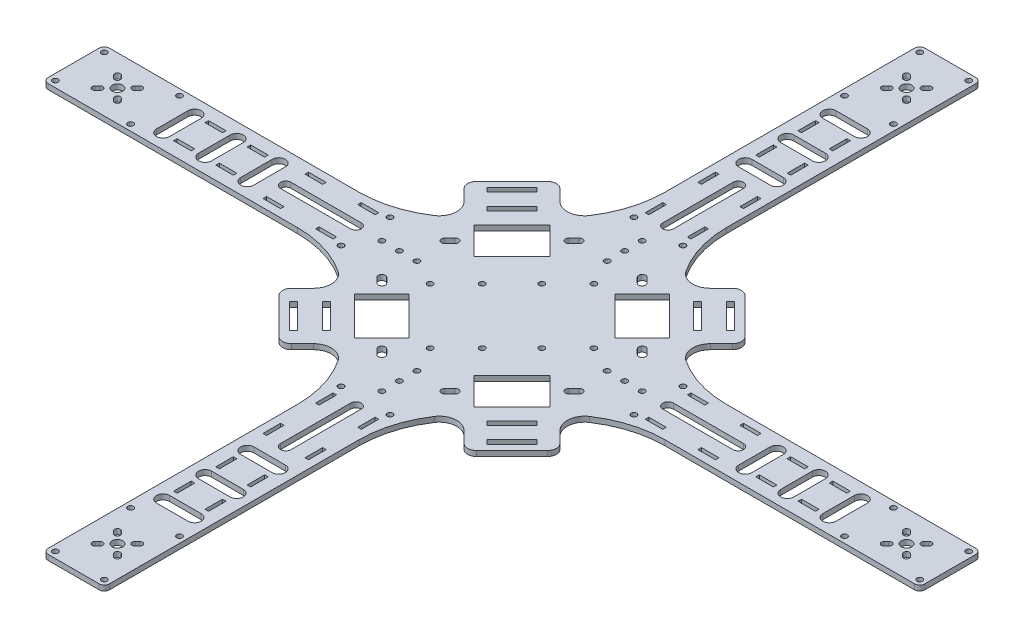
SolidWorks part; units mm, degrees
ref_plane "前视基准面" through (0, 0, 0) normal (0, 0, 1) x (1, 0, 0)
ref_plane "上视基准面" through (0, 0, 0) normal (0, 1, 0) x (1, 0, 0)
ref_plane "右视基准面" through (0, 0, 0) normal (1, 0, 0) x (0, 0, -1)
other "质心 (COM)"
other "Configuration Table"
sketch "基本底盘" plane through (0, 0, 0) normal (0, 1, 0) x (1, 0, 0)
  line L0 (0, 0) -> (0, -450) construction
  line L1 (4.9497, -4.9497) -> (6.364, -6.364) construction
  line L4 (6.0811, -3.8184) -> (7.4953, -5.2326)
  line L5 (3.8184, -6.0811) -> (5.2326, -7.4953)
  line L6 (-17.5, 25) -> (17.5, 25)
  line L9 (-4.9497, -4.9497) -> (-6.364, -6.364) construction
  line L10 (-3.8184, -6.0811) -> (-5.2326, -7.4953)
  line L11 (-6.0811, -3.8184) -> (-7.4953, -5.2326)
  line L12 (-17.5, 25) -> (-17.5, -25)
  line L15 (-4.9497, 4.9497) -> (-6.364, 6.364) construction
  line L16 (-6.0811, 3.8184) -> (-7.4953, 5.2326)
  line L17 (-3.8184, 6.0811) -> (-5.2326, 7.4953)
  line L18 (17.5, 25) -> (17.5, -25)
  line L21 (4.9497, 4.9497) -> (6.364, 6.364) construction
  line L22 (3.8184, 6.0811) -> (5.2326, 7.4953)
  line L23 (6.0811, 3.8184) -> (7.4953, 5.2326)
  line L24 (0, -25) -> (0, -35)
  line L25 (-9, -35) -> (9, -35) construction
  line L26 (-9, -59) -> (9, -59) construction
  line L27 (-17.5, -25) -> (17.5, -25) construction
  line L28 (-17.5, 25) -> (17.5, -25) construction
  line L29 (17.5, 25) -> (-17.5, -25) construction
  line L30 (-17.5, 25) -> (-13.9645, 21.4645)
  line L31 (-17.5, 0) -> (17.5, 0) construction
  line L36 (-225, -225) -> (225, -225) construction
  line L38 (-13.9645, -21.4645) -> (-13.9645, -95) construction
  line L39 (-17.5, -25) -> (-17.5, -120.1472)
  line L40 (17.5, -25) -> (17.5, -120.1472)
  line L42 (-9, -31.25) -> (9, -31.25)
  line L43 (-9, -38.75) -> (9, -38.75)
  line L44 (-9, -55.25) -> (9, -55.25)
  line L45 (-9, -62.75) -> (9, -62.75)
  line L46 (-9, -83) -> (9, -83) construction
  line L47 (-9, -79.25) -> (9, -79.25)
  line L48 (-9, -86.75) -> (9, -86.75)
  line L49 (9, -38.75) -> (9, -55.25)
  line L50 (7.939, -42) -> (9.939, -42)
  line L51 (7.939, -42) -> (7.939, -52)
  line L52 (9.939, -42) -> (9.939, -52)
  line L53 (7.939, -52) -> (9.939, -52)
  line L54 (7.939, -42) -> (9.939, -52) construction
  line L55 (9.939, -42) -> (7.939, -52) construction
  line L56 (7.939, -66.0412) -> (9.939, -76.0412) construction
  line L57 (9.939, -66.0412) -> (7.939, -76.0412) construction
  line L58 (7.939, -66.0412) -> (9.939, -66.0412)
  line L59 (7.939, -66.0412) -> (7.939, -76.0412)
  line L60 (7.939, -76.0412) -> (9.939, -76.0412)
  line L61 (9.939, -66.0412) -> (9.939, -76.0412)
  line L62 (-7.939, -66.0412) -> (-7.939, -76.0412)
  line L63 (-7.939, -76.0412) -> (-9.939, -76.0412)
  line L64 (-9.939, -66.0412) -> (-9.939, -76.0412)
  line L65 (-7.939, -66.0412) -> (-9.939, -66.0412)
  line L66 (-7.939, -52) -> (-9.939, -52)
  line L67 (-7.939, -42) -> (-7.939, -52)
  line L68 (-7.939, -42) -> (-9.939, -42)
  line L69 (-9.939, -42) -> (-9.939, -52)
  line L90 (0, -136) -> (0, -96) construction
  line L92 (-3, -136) -> (-3, -96)
  line L93 (3, -136) -> (3, -96)
  line L94 (11, -96) -> (13, -96)
  line L95 (13, -96) -> (13, -106)
  line L96 (11, -106) -> (13, -106)
  line L97 (11, -96) -> (11, -106)
  line L98 (-11, -96) -> (-11, -106)
  line L99 (-11, -106) -> (-13, -106)
  line L100 (-13, -96) -> (-13, -106)
  line L101 (-11, -96) -> (-13, -96)
  line L102 (-17.5, -116) -> (17.5, -116) construction
  line L103 (-11, -136) -> (-13, -136)
  line L104 (-13, -136) -> (-13, -126)
  line L105 (-11, -126) -> (-13, -126)
  line L106 (-11, -136) -> (-11, -126)
  line L107 (11, -136) -> (11, -126)
  line L108 (11, -126) -> (13, -126)
  line L109 (13, -136) -> (13, -126)
  line L110 (11, -136) -> (13, -136)
  line L111 (250, -207.5) -> (250, -242.5)
  line L112 (250, -207.5) -> (200, -207.5)
  line L113 (250, -242.5) -> (200, -242.5)
  line L114 (200, -225) -> (190, -225)
  line L115 (250, -207.5) -> (246.4645, -211.0355)
  line L116 (200, -207.5) -> (104.8528, -207.5)
  line L117 (200, -242.5) -> (104.8528, -242.5)
  line L118 (186.25, -234) -> (169.75, -234)
  line L119 (183, -232.939) -> (183, -234.939)
  line L120 (183, -232.939) -> (173, -232.939)
  line L121 (183, -234.939) -> (173, -234.939)
  line L122 (173, -232.939) -> (173, -234.939)
  line L123 (158.9588, -232.939) -> (158.9588, -234.939)
  line L124 (158.9588, -232.939) -> (148.9588, -232.939)
  line L125 (148.9588, -232.939) -> (148.9588, -234.939)
  line L126 (158.9588, -234.939) -> (148.9588, -234.939)
  line L127 (158.9588, -217.061) -> (148.9588, -217.061)
  line L128 (148.9588, -217.061) -> (148.9588, -215.061)
  line L129 (158.9588, -215.061) -> (148.9588, -215.061)
  line L130 (158.9588, -217.061) -> (158.9588, -215.061)
  line L131 (173, -217.061) -> (173, -215.061)
  line L132 (183, -217.061) -> (173, -217.061)
  line L133 (183, -217.061) -> (183, -215.061)
  line L134 (183, -215.061) -> (173, -215.061)
  line L135 (129, -236) -> (129, -238)
  line L136 (129, -238) -> (119, -238)
  line L137 (119, -236) -> (119, -238)
  line L138 (129, -236) -> (119, -236)
  line L139 (129, -214) -> (119, -214)
  line L140 (119, -214) -> (119, -212)
  line L141 (129, -212) -> (119, -212)
  line L142 (129, -214) -> (129, -212)
  line L143 (89, -214) -> (89, -212)
  line L144 (89, -212) -> (99, -212)
  line L145 (99, -214) -> (99, -212)
  line L146 (89, -214) -> (99, -214)
  line L147 (89, -236) -> (99, -236)
  line L148 (99, -236) -> (99, -238)
  line L149 (89, -238) -> (99, -238)
  line L150 (89, -236) -> (89, -238)
  line L151 (200, -207.5) -> (200, -242.5) construction
  line L152 (250, -207.5) -> (200, -242.5) construction
  line L153 (250, -242.5) -> (200, -207.5) construction
  line L154 (225, -207.5) -> (225, -242.5) construction
  line L155 (203.5355, -211.0355) -> (130, -211.0355) construction
  line L156 (183, -232.939) -> (173, -234.939) construction
  line L157 (183, -234.939) -> (173, -232.939) construction
  line L158 (158.9588, -232.939) -> (148.9588, -234.939) construction
  line L159 (158.9588, -234.939) -> (148.9588, -232.939) construction
  line L160 (109, -207.5) -> (109, -242.5) construction
  line L161 (220.0503, -229.9497) -> (218.636, -231.364) construction
  line L162 (221.1816, -231.0811) -> (219.7674, -232.4953)
  line L163 (218.9189, -228.8184) -> (217.5047, -230.2326)
  line L164 (220.0503, -220.0503) -> (218.636, -218.636) construction
  line L165 (218.9189, -221.1816) -> (217.5047, -219.7674)
  line L166 (221.1816, -218.9189) -> (219.7674, -217.5047)
  line L167 (229.9497, -220.0503) -> (231.364, -218.636) construction
  line L168 (228.8184, -218.9189) -> (230.2326, -217.5047)
  line L169 (231.0811, -221.1816) -> (232.4953, -219.7674)
  line L170 (229.9497, -229.9497) -> (231.364, -231.364) construction
  line L171 (231.0811, -228.8184) -> (232.4953, -230.2326)
  line L172 (228.8184, -231.0811) -> (230.2326, -232.4953)
  line L173 (190, -216) -> (190, -234) construction
  line L174 (193.75, -216) -> (193.75, -234)
  line L175 (186.25, -216) -> (186.25, -234)
  line L176 (166, -216) -> (166, -234) construction
  line L177 (169.75, -216) -> (169.75, -234)
  line L178 (162.25, -216) -> (162.25, -234)
  line L179 (142, -216) -> (142, -234) construction
  line L180 (145.75, -216) -> (145.75, -234)
  line L181 (138.25, -216) -> (138.25, -234)
  line L182 (89, -225) -> (129, -225) construction
  line L183 (89, -222) -> (129, -222)
  line L184 (89, -228) -> (129, -228)
  line L185 (17.5, -475) -> (-17.5, -475)
  line L186 (17.5, -475) -> (17.5, -425)
  line L187 (-17.5, -475) -> (-17.5, -425)
  line L188 (0, -425) -> (0, -415)
  line L189 (17.5, -475) -> (13.9645, -471.4645)
  line L190 (17.5, -425) -> (17.5, -329.8528)
  line L191 (-17.5, -425) -> (-17.5, -329.8528)
  line L192 (-9, -411.25) -> (-9, -394.75)
  line L193 (-7.939, -408) -> (-9.939, -408)
  line L194 (-7.939, -408) -> (-7.939, -398)
  line L195 (-9.939, -408) -> (-9.939, -398)
  line L196 (-7.939, -398) -> (-9.939, -398)
  line L197 (-7.939, -383.9588) -> (-9.939, -383.9588)
  line L198 (-7.939, -383.9588) -> (-7.939, -373.9588)
  line L199 (-7.939, -373.9588) -> (-9.939, -373.9588)
  line L200 (-9.939, -383.9588) -> (-9.939, -373.9588)
  line L201 (7.939, -383.9588) -> (7.939, -373.9588)
  line L202 (7.939, -373.9588) -> (9.939, -373.9588)
  line L203 (9.939, -383.9588) -> (9.939, -373.9588)
  line L204 (7.939, -383.9588) -> (9.939, -383.9588)
  line L205 (7.939, -398) -> (9.939, -398)
  line L206 (7.939, -408) -> (7.939, -398)
  line L207 (7.939, -408) -> (9.939, -408)
  line L208 (9.939, -408) -> (9.939, -398)
  line L209 (-11, -354) -> (-13, -354)
  line L210 (-13, -354) -> (-13, -344)
  line L211 (-11, -344) -> (-13, -344)
  line L212 (-11, -354) -> (-11, -344)
  line L213 (11, -354) -> (11, -344)
  line L214 (11, -344) -> (13, -344)
  line L215 (13, -354) -> (13, -344)
  line L216 (11, -354) -> (13, -354)
  line L217 (11, -314) -> (13, -314)
  line L218 (13, -314) -> (13, -324)
  line L219 (11, -324) -> (13, -324)
  line L220 (11, -314) -> (11, -324)
  line L221 (-11, -314) -> (-11, -324)
  line L222 (-11, -324) -> (-13, -324)
  line L223 (-13, -314) -> (-13, -324)
  line L224 (-11, -314) -> (-13, -314)
  line L225 (17.5, -425) -> (-17.5, -425) construction
  line L226 (17.5, -475) -> (-17.5, -425) construction
  line L227 (-17.5, -475) -> (17.5, -425) construction
  line L228 (17.5, -450) -> (-17.5, -450) construction
  line L229 (13.9645, -428.5355) -> (13.9645, -355) construction
  line L230 (-7.939, -408) -> (-9.939, -398) construction
  line L231 (-9.939, -408) -> (-7.939, -398) construction
  line L232 (-7.939, -383.9588) -> (-9.939, -373.9588) construction
  line L233 (-9.939, -383.9588) -> (-7.939, -373.9588) construction
  line L234 (17.5, -334) -> (-17.5, -334) construction
  line L235 (-4.9497, -445.0503) -> (-6.364, -443.636) construction
  line L236 (-6.0811, -446.1816) -> (-7.4953, -444.7674)
  line L237 (-3.8184, -443.9189) -> (-5.2326, -442.5047)
  line L238 (4.9497, -445.0503) -> (6.364, -443.636) construction
  line L239 (3.8184, -443.9189) -> (5.2326, -442.5047)
  line L240 (6.0811, -446.1816) -> (7.4953, -444.7674)
  line L241 (4.9497, -454.9497) -> (6.364, -456.364) construction
  line L242 (6.0811, -453.8184) -> (7.4953, -455.2326)
  line L243 (3.8184, -456.0811) -> (5.2326, -457.4953)
  line L244 (-4.9497, -454.9497) -> (-6.364, -456.364) construction
  line L245 (-3.8184, -456.0811) -> (-5.2326, -457.4953)
  line L246 (-6.0811, -453.8184) -> (-7.4953, -455.2326)
  line L247 (9, -415) -> (-9, -415) construction
  line L248 (9, -418.75) -> (-9, -418.75)
  line L249 (9, -411.25) -> (-9, -411.25)
  line L250 (9, -391) -> (-9, -391) construction
  line L251 (9, -394.75) -> (-9, -394.75)
  line L252 (9, -387.25) -> (-9, -387.25)
  line L253 (9, -367) -> (-9, -367) construction
  line L254 (9, -370.75) -> (-9, -370.75)
  line L255 (9, -363.25) -> (-9, -363.25)
  line L256 (0, -314) -> (0, -354) construction
  line L257 (3, -314) -> (3, -354)
  line L258 (-3, -314) -> (-3, -354)
  line L259 (-250, -242.5) -> (-250, -207.5)
  line L260 (-250, -242.5) -> (-200, -242.5)
  line L261 (-250, -207.5) -> (-200, -207.5)
  line L262 (-200, -225) -> (-190, -225)
  line L263 (-250, -242.5) -> (-246.4645, -238.9645)
  line L264 (-200, -242.5) -> (-104.8528, -242.5)
  line L265 (-200, -207.5) -> (-104.8528, -207.5)
  line L266 (-186.25, -216) -> (-169.75, -216)
  line L267 (-183, -217.061) -> (-183, -215.061)
  line L268 (-183, -217.061) -> (-173, -217.061)
  line L269 (-183, -215.061) -> (-173, -215.061)
  line L270 (-173, -217.061) -> (-173, -215.061)
  line L271 (-158.9588, -217.061) -> (-158.9588, -215.061)
  line L272 (-158.9588, -217.061) -> (-148.9588, -217.061)
  line L273 (-148.9588, -217.061) -> (-148.9588, -215.061)
  line L274 (-158.9588, -215.061) -> (-148.9588, -215.061)
  line L275 (-158.9588, -232.939) -> (-148.9588, -232.939)
  line L276 (-148.9588, -232.939) -> (-148.9588, -234.939)
  line L277 (-158.9588, -234.939) -> (-148.9588, -234.939)
  line L278 (-158.9588, -232.939) -> (-158.9588, -234.939)
  line L279 (-173, -232.939) -> (-173, -234.939)
  line L280 (-183, -232.939) -> (-173, -232.939)
  line L281 (-183, -232.939) -> (-183, -234.939)
  line L282 (-183, -234.939) -> (-173, -234.939)
  line L283 (-129, -214) -> (-129, -212)
  line L284 (-129, -212) -> (-119, -212)
  line L285 (-119, -214) -> (-119, -212)
  line L286 (-129, -214) -> (-119, -214)
  line L287 (-129, -236) -> (-119, -236)
  line L288 (-119, -236) -> (-119, -238)
  line L289 (-129, -238) -> (-119, -238)
  line L290 (-129, -236) -> (-129, -238)
  line L291 (-89, -236) -> (-89, -238)
  line L292 (-89, -238) -> (-99, -238)
  line L293 (-99, -236) -> (-99, -238)
  line L294 (-89, -236) -> (-99, -236)
  line L295 (-89, -214) -> (-99, -214)
  line L296 (-99, -214) -> (-99, -212)
  line L297 (-89, -212) -> (-99, -212)
  line L298 (-89, -214) -> (-89, -212)
  line L299 (-200, -242.5) -> (-200, -207.5) construction
  line L300 (-250, -242.5) -> (-200, -207.5) construction
  line L301 (-250, -207.5) -> (-200, -242.5) construction
  line L302 (-225, -242.5) -> (-225, -207.5) construction
  line L303 (-203.5355, -238.9645) -> (-130, -238.9645) construction
  line L304 (-183, -217.061) -> (-173, -215.061) construction
  line L305 (-183, -215.061) -> (-173, -217.061) construction
  line L306 (-158.9588, -217.061) -> (-148.9588, -215.061) construction
  line L307 (-158.9588, -215.061) -> (-148.9588, -217.061) construction
  line L308 (-109, -242.5) -> (-109, -207.5) construction
  line L309 (-220.0503, -220.0503) -> (-218.636, -218.636) construction
  line L310 (-221.1816, -218.9189) -> (-219.7674, -217.5047)
  line L311 (-218.9189, -221.1816) -> (-217.5047, -219.7674)
  line L312 (-220.0503, -229.9497) -> (-218.636, -231.364) construction
  line L313 (-218.9189, -228.8184) -> (-217.5047, -230.2326)
  line L314 (-221.1816, -231.0811) -> (-219.7674, -232.4953)
  line L315 (-229.9497, -229.9497) -> (-231.364, -231.364) construction
  line L316 (-228.8184, -231.0811) -> (-230.2326, -232.4953)
  line L317 (-231.0811, -228.8184) -> (-232.4953, -230.2326)
  line L318 (-229.9497, -220.0503) -> (-231.364, -218.636) construction
  line L319 (-231.0811, -221.1816) -> (-232.4953, -219.7674)
  line L320 (-228.8184, -218.9189) -> (-230.2326, -217.5047)
  line L321 (-190, -234) -> (-190, -216) construction
  line L322 (-193.75, -234) -> (-193.75, -216)
  line L323 (-186.25, -234) -> (-186.25, -216)
  line L324 (-166, -234) -> (-166, -216) construction
  line L325 (-169.75, -234) -> (-169.75, -216)
  line L326 (-162.25, -234) -> (-162.25, -216)
  line L327 (-142, -234) -> (-142, -216) construction
  line L328 (-145.75, -234) -> (-145.75, -216)
  line L329 (-138.25, -234) -> (-138.25, -216)
  line L330 (-89, -225) -> (-129, -225) construction
  line L331 (-89, -228) -> (-129, -228)
  line L332 (-89, -222) -> (-129, -222)
  line L333 (-35.0736, -162.5736) -> (-62.4264, -189.9264) construction
  line L334 (35.0736, -162.5736) -> (62.4264, -189.9264) construction
  line L335 (-62.4264, -260.0736) -> (-35.0736, -287.4264) construction
  line L336 (62.4264, -260.0736) -> (35.0736, -287.4264) construction
  line L337 (-62.4264, -189.9264) -> (-35.0736, -162.5736) construction
  line L338 (-70.2118, -182.141) -> (-80.1041, -172.2487)
  line L339 (-42.859, -154.7882) -> (-52.7513, -144.8959)
  line L340 (-80.1041, -172.2487) -> (-52.7513, -144.8959)
  line L341 (35.0736, -162.5736) -> (62.4264, -189.9264) construction
  line L342 (42.859, -154.7882) -> (52.7513, -144.8959)
  line L343 (52.7513, -144.8959) -> (80.1041, -172.2487)
  line L344 (70.2118, -182.141) -> (80.1041, -172.2487)
  line L345 (62.4264, -260.0736) -> (35.0736, -287.4264) construction
  line L346 (70.2118, -267.859) -> (80.1041, -277.7513)
  line L347 (80.1041, -277.7513) -> (52.7513, -305.1041)
  line L348 (42.859, -295.2118) -> (52.7513, -305.1041)
  line L349 (-35.0736, -287.4264) -> (-62.4264, -260.0736) construction
  line L350 (-42.859, -295.2118) -> (-52.7513, -305.1041)
  line L351 (-52.7513, -305.1041) -> (-80.1041, -277.7513)
  line L352 (-70.2118, -267.859) -> (-80.1041, -277.7513)
  circle A0 centre (0, 0) radius 8 construction
  arc A3 (6.0811, -3.8184) -> (3.8184, -6.0811) centre (4.9497, -4.9497) ccw
  arc A4 (5.2326, -7.4953) -> (7.4953, -5.2326) centre (6.364, -6.364) ccw
  arc A7 (-3.8184, -6.0811) -> (-6.0811, -3.8184) centre (-4.9497, -4.9497) ccw
  arc A8 (-7.4953, -5.2326) -> (-5.2326, -7.4953) centre (-6.364, -6.364) ccw
  arc A11 (-6.0811, 3.8184) -> (-3.8184, 6.0811) centre (-4.9497, 4.9497) ccw
  arc A12 (-5.2326, 7.4953) -> (-7.4953, 5.2326) centre (-6.364, 6.364) ccw
  arc A15 (3.8184, 6.0811) -> (6.0811, 3.8184) centre (4.9497, 4.9497) ccw
  arc A16 (7.4953, 5.2326) -> (5.2326, 7.4953) centre (6.364, 6.364) ccw
  circle A17 centre (0, 0) radius 14 construction
  arc A18 (-9, -31.25) -> (-9, -38.75) centre (-9, -35) ccw
  arc A19 (9, -38.75) -> (9, -31.25) centre (9, -35) ccw
  circle A20 centre (0, 0) radius 3
  circle A21 centre (0, 0) radius 88.9 construction
  circle A22 centre (0, 0) radius 64.77 construction
  circle A23 centre (-13.9645, 21.4645) radius 1.6
  circle A24 centre (13.9645, 21.4645) radius 1.6
  circle A25 centre (13.9645, -21.4645) radius 1.6
  circle A26 centre (-13.9645, -21.4645) radius 1.6
  arc A30 (-9, -55.25) -> (-9, -62.75) centre (-9, -59) ccw
  arc A31 (9, -62.75) -> (9, -55.25) centre (9, -59) ccw
  arc A32 (-9, -79.25) -> (-9, -86.75) centre (-9, -83) ccw
  arc A33 (9, -86.75) -> (9, -79.25) centre (9, -83) ccw
  arc A34 (-3, -136) -> (3, -136) centre (0, -136) ccw
  arc A35 (3, -96) -> (-3, -96) centre (0, -96) ccw
  circle A36 centre (225, -225) radius 3
  circle A37 centre (246.4645, -211.0355) radius 1.6
  circle A38 centre (246.4645, -238.9645) radius 1.6
  circle A39 centre (203.5355, -238.9645) radius 1.6
  circle A40 centre (203.5355, -211.0355) radius 1.6
  circle A41 centre (225, -225) radius 8 construction
  circle A42 centre (225, -225) radius 14 construction
  circle A43 centre (225, -225) radius 88.9 construction
  circle A44 centre (225, -225) radius 64.77 construction
  arc A45 (221.1816, -231.0811) -> (218.9189, -228.8184) centre (220.0503, -229.9497) ccw
  arc A46 (217.5047, -230.2326) -> (219.7674, -232.4953) centre (218.636, -231.364) ccw
  arc A47 (218.9189, -221.1816) -> (221.1816, -218.9189) centre (220.0503, -220.0503) ccw
  arc A48 (219.7674, -217.5047) -> (217.5047, -219.7674) centre (218.636, -218.636) ccw
  arc A49 (228.8184, -218.9189) -> (231.0811, -221.1816) centre (229.9497, -220.0503) ccw
  arc A50 (232.4953, -219.7674) -> (230.2326, -217.5047) centre (231.364, -218.636) ccw
  arc A51 (231.0811, -228.8184) -> (228.8184, -231.0811) centre (229.9497, -229.9497) ccw
  arc A52 (230.2326, -232.4953) -> (232.4953, -230.2326) centre (231.364, -231.364) ccw
  arc A53 (193.75, -216) -> (186.25, -216) centre (190, -216) ccw
  arc A54 (186.25, -234) -> (193.75, -234) centre (190, -234) ccw
  arc A55 (169.75, -216) -> (162.25, -216) centre (166, -216) ccw
  arc A56 (162.25, -234) -> (169.75, -234) centre (166, -234) ccw
  arc A57 (145.75, -216) -> (138.25, -216) centre (142, -216) ccw
  arc A58 (138.25, -234) -> (145.75, -234) centre (142, -234) ccw
  arc A59 (89, -222) -> (89, -228) centre (89, -225) ccw
  arc A60 (129, -228) -> (129, -222) centre (129, -225) ccw
  circle A61 centre (0, -450) radius 3
  circle A62 centre (13.9645, -471.4645) radius 1.6
  circle A63 centre (-13.9645, -471.4645) radius 1.6
  circle A64 centre (-13.9645, -428.5355) radius 1.6
  circle A65 centre (13.9645, -428.5355) radius 1.6
  circle A66 centre (0, -450) radius 8 construction
  circle A67 centre (0, -450) radius 14 construction
  circle A68 centre (0, -450) radius 88.9 construction
  circle A69 centre (0, -450) radius 64.77 construction
  arc A70 (-6.0811, -446.1816) -> (-3.8184, -443.9189) centre (-4.9497, -445.0503) ccw
  arc A71 (-5.2326, -442.5047) -> (-7.4953, -444.7674) centre (-6.364, -443.636) ccw
  arc A72 (3.8184, -443.9189) -> (6.0811, -446.1816) centre (4.9497, -445.0503) ccw
  arc A73 (7.4953, -444.7674) -> (5.2326, -442.5047) centre (6.364, -443.636) ccw
  arc A74 (6.0811, -453.8184) -> (3.8184, -456.0811) centre (4.9497, -454.9497) ccw
  arc A75 (5.2326, -457.4953) -> (7.4953, -455.2326) centre (6.364, -456.364) ccw
  arc A76 (-3.8184, -456.0811) -> (-6.0811, -453.8184) centre (-4.9497, -454.9497) ccw
  arc A77 (-7.4953, -455.2326) -> (-5.2326, -457.4953) centre (-6.364, -456.364) ccw
  arc A78 (9, -418.75) -> (9, -411.25) centre (9, -415) ccw
  arc A79 (-9, -411.25) -> (-9, -418.75) centre (-9, -415) ccw
  arc A80 (9, -394.75) -> (9, -387.25) centre (9, -391) ccw
  arc A81 (-9, -387.25) -> (-9, -394.75) centre (-9, -391) ccw
  arc A82 (9, -370.75) -> (9, -363.25) centre (9, -367) ccw
  arc A83 (-9, -363.25) -> (-9, -370.75) centre (-9, -367) ccw
  arc A84 (3, -314) -> (-3, -314) centre (0, -314) ccw
  arc A85 (-3, -354) -> (3, -354) centre (0, -354) ccw
  circle A86 centre (-225, -225) radius 3
  circle A87 centre (-246.4645, -238.9645) radius 1.6
  circle A88 centre (-246.4645, -211.0355) radius 1.6
  circle A89 centre (-203.5355, -211.0355) radius 1.6
  circle A90 centre (-203.5355, -238.9645) radius 1.6
  circle A91 centre (-225, -225) radius 8 construction
  circle A92 centre (-225, -225) radius 14 construction
  circle A93 centre (-225, -225) radius 88.9 construction
  circle A94 centre (-225, -225) radius 64.77 construction
  arc A95 (-221.1816, -218.9189) -> (-218.9189, -221.1816) centre (-220.0503, -220.0503) ccw
  arc A96 (-217.5047, -219.7674) -> (-219.7674, -217.5047) centre (-218.636, -218.636) ccw
  arc A97 (-218.9189, -228.8184) -> (-221.1816, -231.0811) centre (-220.0503, -229.9497) ccw
  arc A98 (-219.7674, -232.4953) -> (-217.5047, -230.2326) centre (-218.636, -231.364) ccw
  arc A99 (-228.8184, -231.0811) -> (-231.0811, -228.8184) centre (-229.9497, -229.9497) ccw
  arc A100 (-232.4953, -230.2326) -> (-230.2326, -232.4953) centre (-231.364, -231.364) ccw
  arc A101 (-231.0811, -221.1816) -> (-228.8184, -218.9189) centre (-229.9497, -220.0503) ccw
  arc A102 (-230.2326, -217.5047) -> (-232.4953, -219.7674) centre (-231.364, -218.636) ccw
  arc A103 (-193.75, -234) -> (-186.25, -234) centre (-190, -234) ccw
  arc A104 (-186.25, -216) -> (-193.75, -216) centre (-190, -216) ccw
  arc A105 (-169.75, -234) -> (-162.25, -234) centre (-166, -234) ccw
  arc A106 (-162.25, -216) -> (-169.75, -216) centre (-166, -216) ccw
  arc A107 (-145.75, -234) -> (-138.25, -234) centre (-142, -234) ccw
  arc A108 (-138.25, -216) -> (-145.75, -216) centre (-142, -216) ccw
  arc A109 (-89, -228) -> (-89, -222) centre (-89, -225) ccw
  arc A110 (-129, -222) -> (-129, -228) centre (-129, -225) ccw
  circle A111 centre (-13.9645, -141.4645) radius 1.6
  circle A112 centre (13.9645, -141.4645) radius 1.6
  circle A113 centre (83.5355, -211.0355) radius 1.6
  circle A114 centre (83.5355, -238.9645) radius 1.6
  circle A115 centre (13.9645, -308.5355) radius 1.6
  circle A116 centre (-13.9645, -308.5355) radius 1.6
  circle A117 centre (-83.5355, -238.9645) radius 1.6
  circle A118 centre (-83.5355, -211.0355) radius 1.6
  arc A119 (104.8528, -242.5) -> (71.7689, -252.4455) centre (104.8528, -302.5) ccw
  arc A120 (104.8528, -207.5) -> (71.7689, -197.5545) centre (104.8528, -147.5) cw
  arc A121 (17.5, -329.8528) -> (27.4455, -296.7689) centre (77.5, -329.8528) cw
  arc A122 (-17.5, -329.8528) -> (-27.4455, -296.7689) centre (-77.5, -329.8528) ccw
  arc A123 (-71.7689, -252.4455) -> (-104.8528, -242.5) centre (-104.8528, -302.5) ccw
  arc A124 (-104.8528, -207.5) -> (-71.7689, -197.5545) centre (-104.8528, -147.5) ccw
  arc A125 (27.4455, -153.2311) -> (17.5, -120.1472) centre (77.5, -120.1472) cw
  arc A126 (-27.4455, -153.2311) -> (-17.5, -120.1472) centre (-77.5, -120.1472) ccw
  arc A127 (-27.4455, -296.7689) -> (-42.859, -295.2118) centre (-35.7879, -302.2829) ccw
  arc A128 (-70.2118, -267.859) -> (-71.7689, -252.4455) centre (-77.2829, -260.7879) ccw
  arc A129 (70.2118, -267.859) -> (71.7689, -252.4455) centre (77.2829, -260.7879) cw
  arc A130 (27.4455, -296.7689) -> (42.859, -295.2118) centre (35.7879, -302.2829) cw
  arc A131 (71.7689, -197.5545) -> (70.2118, -182.141) centre (77.2829, -189.2121) cw
  arc A132 (42.859, -154.7882) -> (27.4455, -153.2311) centre (35.7879, -147.7171) cw
  arc A133 (-27.4455, -153.2311) -> (-42.859, -154.7882) centre (-35.7879, -147.7171) cw
  arc A134 (-71.7689, -197.5545) -> (-70.2118, -182.141) centre (-77.2829, -189.2121) ccw
  point P14 (5.6569, -5.6569)
  point P28 (-5.6569, -5.6569)
  point P34 (0, 0)
  point P42 (-5.6569, 5.6569)
  point P51 (0, -225)
  point P56 (5.6569, 5.6569)
  point P61 (0, 0)
  point P63 (0, 8)
  point P71 (0, -116)
  point P73 (0, -35)
  point P80 (0, -59)
  point P87 (0, -83)
  point P93 (8.939, -47)
  point P95 (8.939, -71.0412)
  point P124 (0, -116)
  point P143 (219.3431, -230.6569)
  point P157 (219.3431, -219.3431)
  point P163 (225, -225)
  point P171 (230.6569, -219.3431)
  point P181 (230.6569, -230.6569)
  point P186 (225, -225)
  point P195 (109, -225)
  point P196 (190, -225)
  point P203 (166, -225)
  point P210 (142, -225)
  point P216 (178, -233.939)
  point P218 (153.9588, -233.939)
  point P242 (109, -225)
  point P265 (-5.6569, -444.3431)
  point P279 (5.6569, -444.3431)
  point P285 (0, -450)
  point P293 (5.6569, -455.6569)
  point P303 (-5.6569, -455.6569)
  point P308 (0, -450)
  point P317 (0, -334)
  point P318 (0, -415)
  point P325 (0, -391)
  point P332 (0, -367)
  point P338 (-8.939, -403)
  point P340 (-8.939, -378.9588)
  point P364 (0, -334)
  point P387 (-219.3431, -219.3431)
  point P401 (-219.3431, -230.6569)
  point P407 (-225, -225)
  point P415 (-230.6569, -230.6569)
  point P425 (-230.6569, -219.3431)
  point P432 (-225, -225)
  point P441 (-109, -225)
  point P442 (-190, -225)
  point P449 (-166, -225)
  point P456 (-142, -225)
  point P462 (-178, -216.061)
  point P464 (-153.9588, -216.061)
  point P488 (-109, -225)
  point P499 (0, -225)
  point P516 (0, -225)
  point P547 (0, -225)
  dimension "D1" = 16
  dimension "D3" = 28
  dimension "D2" = 6
  dimension "D4" = 4
  dimension "D5" = 129.54
  dimension "D9" = 3.2
  dimension "D11" = 4
  dimension "D12" = 60
  dimension "D13" = 25
  dimension "D14" = 10
  dimension "D15" = 3
  dimension "D20" = 10
  dimension "D10" = 2
  dimension "D6" = 35
  dimension "D7" = 50
  dimension "D8" = 5
  dimension "D16" = 2
  dimension "D17" = 10
  dimension "D19" = 4
  dimension "D18" = 2
extrude "凸台-拉伸1" add sketch "基本底盘" along normal blind 3 contours A126 L333 A124 L265 L261 L259 A87 L260 L264 A123 L335 A122 L191 L187 L185 A62 L186 L190 A121 L336 A119 L117 L113 L111 A37 L112 L116 A120 L334 A125 L40 L18 L6 A23 L12 L39 A118 A115 A114 region at (0, 0, 225)
sketch "草图2" plane through (0, 3, 0) normal (0, 1, 0) x (1, 0, 0)
  line L0 (-17.6777, -207.3223) -> (17.6777, -242.6777)
  line L1 (24.7487, -200.2513) -> (23.3345, -201.6655)
  line L2 (-24.7487, -249.7487) -> (24.7487, -200.2513)
  line L3 (7.0711, -182.5736) -> (42.4264, -217.9289) construction
  line L4 (7.0711, -182.5736) -> (-42.4264, -232.0711) construction
  line L5 (42.4264, -217.9289) -> (-7.0711, -267.4264) construction
  line L6 (-42.4264, -232.0711) -> (-7.0711, -267.4264) construction
  line L7 (7.0711, -182.5736) -> (-7.0711, -267.4264) construction
  line L8 (42.4264, -217.9289) -> (-42.4264, -232.0711) construction
  line L9 (7.4246, -185.7556) -> (39.2444, -217.5754)
  line L10 (17.6777, -242.6777) -> (37.1231, -262.1231)
  line L11 (19.4454, -279.8008) -> (54.8008, -244.4454) construction
  line L12 (56.215, -243.0312) -> (53.3866, -245.8597) construction
  line L13 (18.0312, -281.215) -> (20.8597, -278.3866) construction
  line L14 (57.6292, -244.4454) -> (54.8008, -247.2739)
  line L15 (54.8008, -241.617) -> (51.9723, -244.4454)
  line L16 (19.4454, -282.6292) -> (22.2739, -279.8008)
  line L17 (16.617, -279.8008) -> (19.4454, -276.9723)
  line L18 (-18.0312, -281.215) -> (-20.8597, -278.3866) construction
  line L19 (-19.4454, -282.6292) -> (-22.2739, -279.8008)
  line L20 (-16.617, -279.8008) -> (-19.4454, -276.9723)
  line L21 (-56.215, -243.0312) -> (-53.3866, -245.8597) construction
  line L22 (-57.6292, -244.4454) -> (-54.8008, -247.2739)
  line L23 (-54.8008, -241.617) -> (-51.9723, -244.4454)
  line L24 (-56.215, -206.9688) -> (-53.3866, -204.1403) construction
  line L25 (-57.6292, -205.5546) -> (-54.8008, -202.7261)
  line L26 (-54.8008, -208.383) -> (-51.9723, -205.5546)
  line L27 (-18.0312, -168.785) -> (-20.8597, -171.6134) construction
  line L28 (-19.4454, -167.3708) -> (-22.2739, -170.1992)
  line L29 (-16.617, -170.1992) -> (-19.4454, -173.0277)
  line L30 (18.0312, -168.785) -> (20.8597, -171.6134) construction
  line L31 (19.4454, -167.3708) -> (22.2739, -170.1992)
  line L32 (16.617, -170.1992) -> (19.4454, -173.0277)
  line L33 (56.215, -206.9688) -> (53.3866, -204.1403) construction
  line L34 (57.6292, -205.5546) -> (54.8008, -202.7261)
  line L35 (54.8008, -208.383) -> (51.9723, -205.5546)
  line L36 (18.5616, -265.1283) -> (40.1283, -243.5616)
  line L37 (18.5616, -265.1283) -> (34.1179, -280.6847)
  line L38 (40.1283, -243.5616) -> (55.6847, -259.1179)
  line L39 (34.1179, -280.6847) -> (55.6847, -259.1179)
  line L40 (18.5616, -265.1283) -> (55.6847, -259.1179) construction
  line L41 (40.1283, -243.5616) -> (34.1179, -280.6847) construction
  line L42 (-40.1283, -243.5616) -> (-18.5616, -265.1283)
  line L43 (-40.1283, -243.5616) -> (-55.6847, -259.1179)
  line L44 (-55.6847, -259.1179) -> (-34.1179, -280.6847)
  line L45 (-18.5616, -265.1283) -> (-34.1179, -280.6847)
  line L46 (-18.5616, -184.8717) -> (-40.1283, -206.4384)
  line L47 (-18.5616, -184.8717) -> (-34.1179, -169.3153)
  line L48 (-34.1179, -169.3153) -> (-55.6847, -190.8821)
  line L49 (-40.1283, -206.4384) -> (-55.6847, -190.8821)
  line L50 (40.1283, -206.4384) -> (18.5616, -184.8717)
  line L51 (40.1283, -206.4384) -> (55.6847, -190.8821)
  line L52 (55.6847, -190.8821) -> (34.1179, -169.3153)
  line L53 (18.5616, -184.8717) -> (34.1179, -169.3153)
  line L54 (0, -150.7538) -> (18.0312, -168.785) construction
  line L55 (-19.4454, -170.1992) -> (0, -150.7538) construction
  line L56 (0, 0) -> (0, -450) construction
  line L57 (-66.4277, -158.5723) -> (-57.5888, -167.4112) construction
  line L58 (-80.1041, -172.2487) -> (-52.7513, -144.8959) construction
  line L59 (-64.6599, -174.4822) -> (-50.5178, -160.3401)
  line L60 (-57.5888, -167.4112) -> (-54.0533, -170.9467)
  line L61 (-61.1244, -178.0178) -> (-46.9822, -163.8756)
  line L62 (-46.9822, -163.8756) -> (-44.7195, -166.1384)
  line L63 (-44.7195, -166.1384) -> (-58.8616, -180.2805)
  line L64 (-58.8616, -180.2805) -> (-61.1244, -178.0178)
  line L65 (-56.316, -154.5418) -> (-70.4582, -168.684)
  line L66 (-54.0533, -156.8046) -> (-56.316, -154.5418)
  line L67 (-68.1954, -170.9467) -> (-54.0533, -156.8046)
  line L68 (-70.4582, -168.684) -> (-68.1954, -170.9467)
  line L69 (70.4582, -168.684) -> (56.316, -154.5418)
  line L70 (56.316, -154.5418) -> (54.0533, -156.8046)
  line L71 (54.0533, -156.8046) -> (68.1954, -170.9467)
  line L72 (68.1954, -170.9467) -> (70.4582, -168.684)
  line L73 (44.7195, -166.1384) -> (46.9822, -163.8756)
  line L74 (46.9822, -163.8756) -> (61.1244, -178.0178)
  line L75 (61.1244, -178.0178) -> (58.8616, -180.2805)
  line L76 (58.8616, -180.2805) -> (44.7195, -166.1384)
  line L77 (56.316, -295.4582) -> (70.4582, -281.316)
  line L78 (70.4582, -281.316) -> (68.1954, -279.0533)
  line L79 (68.1954, -279.0533) -> (54.0533, -293.1954)
  line L80 (54.0533, -293.1954) -> (56.316, -295.4582)
  line L81 (58.8616, -269.7195) -> (61.1244, -271.9822)
  line L82 (61.1244, -271.9822) -> (46.9822, -286.1244)
  line L83 (46.9822, -286.1244) -> (44.7195, -283.8616)
  line L84 (44.7195, -283.8616) -> (58.8616, -269.7195)
  line L85 (-70.4582, -281.316) -> (-56.316, -295.4582)
  line L86 (-56.316, -295.4582) -> (-54.0533, -293.1954)
  line L87 (-54.0533, -293.1954) -> (-68.1954, -279.0533)
  line L88 (-68.1954, -279.0533) -> (-70.4582, -281.316)
  line L89 (-44.7195, -283.8616) -> (-46.9822, -286.1244)
  line L90 (-46.9822, -286.1244) -> (-61.1244, -271.9822)
  line L91 (-61.1244, -271.9822) -> (-58.8616, -269.7195)
  line L92 (-58.8616, -269.7195) -> (-44.7195, -283.8616)
  circle A0 centre (39.2444, -217.5754) radius 1.6
  circle A1 centre (7.4246, -185.7556) radius 1.6
  circle A2 centre (7.4246, -249.3952) radius 1.6
  circle A3 centre (-24.3952, -217.5754) radius 1.6
  circle A4 centre (24.3952, -232.4246) radius 1.6
  circle A5 centre (-7.4246, -264.2444) radius 1.6
  circle A6 centre (-39.2444, -232.4246) radius 1.6
  circle A7 centre (-7.4246, -200.6048) radius 1.6
  arc A8 (57.6292, -244.4454) -> (54.8008, -241.617) centre (56.215, -243.0312) ccw
  arc A9 (51.9723, -244.4454) -> (54.8008, -247.2739) centre (53.3866, -245.8597) ccw
  arc A10 (19.4454, -282.6292) -> (16.617, -279.8008) centre (18.0312, -281.215) cw
  arc A11 (19.4454, -276.9723) -> (22.2739, -279.8008) centre (20.8597, -278.3866) cw
  arc A12 (-19.4454, -282.6292) -> (-16.617, -279.8008) centre (-18.0312, -281.215) ccw
  arc A13 (-19.4454, -276.9723) -> (-22.2739, -279.8008) centre (-20.8597, -278.3866) ccw
  arc A14 (-57.6292, -244.4454) -> (-54.8008, -241.617) centre (-56.215, -243.0312) cw
  arc A15 (-51.9723, -244.4454) -> (-54.8008, -247.2739) centre (-53.3866, -245.8597) cw
  arc A16 (-57.6292, -205.5546) -> (-54.8008, -208.383) centre (-56.215, -206.9688) ccw
  arc A17 (-51.9723, -205.5546) -> (-54.8008, -202.7261) centre (-53.3866, -204.1403) ccw
  arc A18 (-19.4454, -167.3708) -> (-16.617, -170.1992) centre (-18.0312, -168.785) cw
  arc A19 (-19.4454, -173.0277) -> (-22.2739, -170.1992) centre (-20.8597, -171.6134) cw
  arc A20 (19.4454, -167.3708) -> (16.617, -170.1992) centre (18.0312, -168.785) ccw
  arc A21 (19.4454, -173.0277) -> (22.2739, -170.1992) centre (20.8597, -171.6134) ccw
  arc A22 (57.6292, -205.5546) -> (54.8008, -208.383) centre (56.215, -206.9688) cw
  arc A23 (51.9723, -205.5546) -> (54.8008, -202.7261) centre (53.3866, -204.1403) cw
  circle A24 centre (0, -150.7538) radius 1.6
  circle A25 centre (0, -160.7538) radius 1.6
  circle A26 centre (0, -170.7538) radius 1.6
  circle A27 centre (74.2462, -225) radius 1.6
  circle A28 centre (64.2462, -225) radius 1.6
  circle A29 centre (54.2462, -225) radius 1.6
  circle A30 centre (0, -299.2462) radius 1.6
  circle A31 centre (0, -289.2462) radius 1.6
  circle A32 centre (0, -279.2462) radius 1.6
  circle A33 centre (-74.2462, -225) radius 1.6
  circle A34 centre (-64.2462, -225) radius 1.6
  circle A35 centre (-54.2462, -225) radius 1.6
  point P3 (0, -225)
  point P7 (0, -225)
  point P8 (0, -225)
  point P12 (23.3345, -201.6655)
  point P34 (37.1231, -262.1231)
  point P38 (54.8008, -244.4454)
  point P43 (19.4454, -279.8008)
  point P55 (-19.4454, -279.8008)
  point P60 (-54.8008, -244.4454)
  point P69 (-54.8008, -205.5546)
  point P74 (-19.4454, -170.1992)
  point P83 (19.4454, -170.1992)
  point P88 (54.8008, -205.5546)
  point P93 (0, -225)
  point P110 (0, -225)
  point P139 (0, -225)
  point P144 (-57.5888, -167.4112)
  point P148 (-54.0533, -170.9467)
  point P181 (0, -225)
  dimension "D4" = 3.2
  dimension "D5" = 3.2
  dimension "D13" = 3.2
  dimension "D1" = 70
  dimension "D2" = 2
  dimension "D3" = 22.5
  dimension "D7" = 27.5
  dimension "D8" = 25
  dimension "D9" = 4
  dimension "D10" = 30.5
  dimension "D11" = 22
  dimension "D16" = 12.5
  dimension "D17" = 10
  dimension "D18" = 5
  dimension "D19" = 10
  dimension "D20" = 3.2
  dimension "D21" = 20
  dimension "D22" = 4
  dimension "D6" = 2
  dimension "D14" = 3
  dimension "D12" = 4
  dimension "D15" = 4
extrude "切除-拉伸1" cut sketch "草图2" against normal blind 10 and the other way through all contours L49 L46 L47 L48 | L53 L50 L51 L52 | A24 | A25 | A26 | L32 A21 L31 A20 | A19 L29 A18 L28 | L26 A17 L25 A16 | A23 L35 A22 L34 | L15 A9 L14 A8 | L37 L39 L38 L36 | A7 | A1 | A3 | A6 | A34 | A33 | A35 | A15 L23 A14 L22 | L45 L42 L43 L44 | A11 L17 A10 L16 | A32 | A31 | L20 A13 L19 A12 | A30 | A5 | A2 | A4 | A0 | A29 | A28 | A27 | A7 region at (35.1079, 3, 249.3245) region at (5.9882, 3, 185.1606) region at (39.8394, 3, 216.139) region at (54.8008, 3, 244.4454) region at (19.4454, 3, 279.8008) region at (-19.4454, 3, 279.8008) region at (-54.8008, 3, 244.4454) region at (-54.8008, 3, 205.5546) region at (-19.4454, 3, 170.1992) region at (19.4454, 3, 170.1992) region at (54.8008, 3, 205.5546) region at (-37.1231, 3, 262.1231) region at (-37.1231, 3, 187.8769) region at (37.1231, 3, 187.8769) region at (7.4246, 3, 249.3952) region at (-24.3952, 3, 217.5754) region at (24.3952, 3, 232.4246) region at (-7.4246, 3, 264.2444) region at (-39.2444, 3, 232.4246) region at (-7.4246, 3, 200.6048) region at (0, 3, 150.7538) region at (0, 3, 160.7538) region at (0, 3, 170.7538) region at (74.2462, 3, 225) region at (64.2462, 3, 225) region at (54.2462, 3, 225) region at (0, 3, 299.2462) region at (0, 3, 289.2462) region at (0, 3, 279.2462) region at (-74.2462, 3, 225) region at (-64.2462, 3, 225) region at (-54.2462, 3, 225)
fillet "圆角1" radius 3 8 edges at (-250, 1.5, 242.5) (-250, 1.5, 207.5) (250, 1.5, 242.5) (250, 1.5, 207.5) (-17.5, 1.5, -25) (17.5, 1.5, -25) (17.5, 1.5, 475) (-17.5, 1.5, 475)
fillet "圆角2" radius 5 8 edges at (-80.1041, 1.5, 172.2487) (-52.7513, 1.5, 144.8959) (52.7513, 1.5, 144.8959) (80.1041, 1.5, 172.2487) (80.1041, 1.5, 277.7513) (52.7513, 1.5, 305.1041) (-52.7513, 1.5, 305.1041) (-80.1041, 1.5, 277.7513)
extrude "切除-拉伸2" cut sketch "草图2<3>" against normal blind 10 and the other way through all contours L65 L68 L67 L66 | L64 L63 L62 L61 | L71 L72 L69 L70 | L76 L75 L74 L73 | L84 L83 L82 L81 | L79 L80 L77 L78 | L87 L88 L85 L86 | L92 L91 L90 L89 region at (-52.9219, 3, 172.0781) region at (-62.2557, 3, 162.7443) region at (62.2557, 3, 162.7443) region at (52.9219, 3, 172.0781) region at (62.2557, 3, 287.2557) region at (52.9219, 3, 277.9219) region at (-62.2557, 3, 287.2557) region at (-52.9219, 3, 277.9219)
sketch "草图2<3>" plane through (0, 3, 0) normal (0, 1, 0) x (1, 0, 0) same geometry as "草图2"
